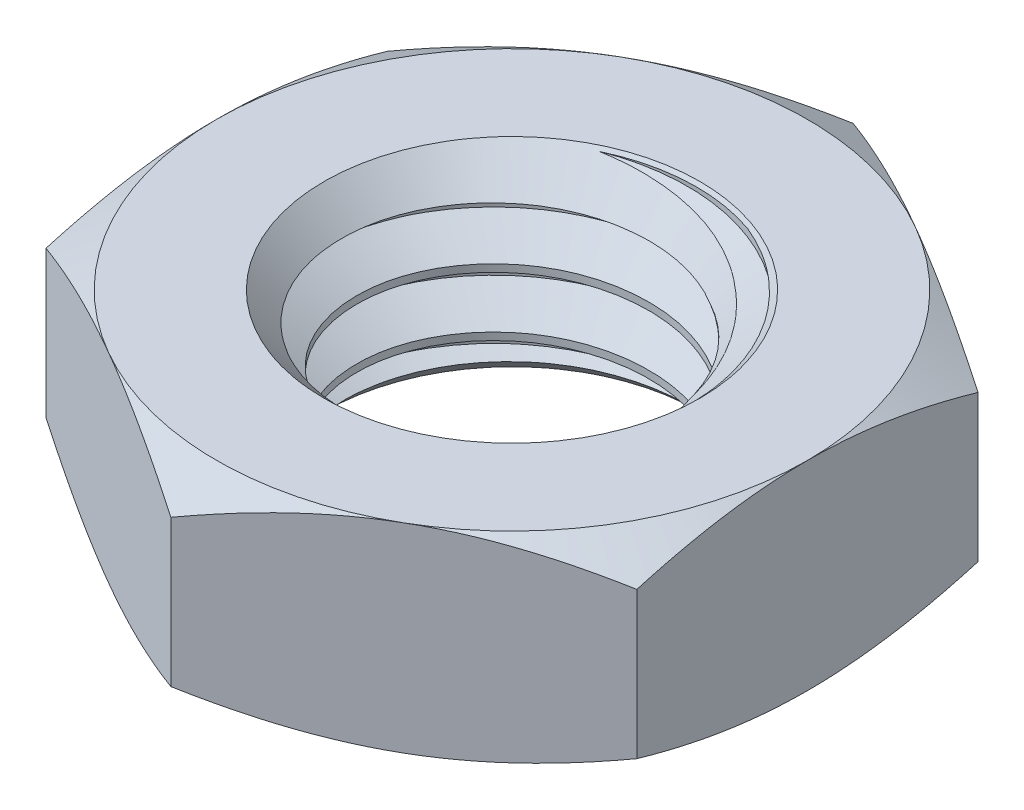
SolidWorks part; units mm, degrees
ref_plane "Front Plane" through (0, 0, 0) normal (0, 0, 1) x (1, 0, 0)
ref_plane "Top Plane" through (0, 0, 0) normal (0, 1, 0) x (1, 0, 0)
ref_plane "Right Plane" through (0, 0, 0) normal (1, 0, 0) x (0, 0, -1)
sketch "Sketch8" plane through (0, 0, 0) normal (0, 1, 0) x (1, 0, 0)
  line L0 (-4, 0) -> (4, 0) construction
  line L1 (0, 2.5) -> (0, -2.5) construction
  line L2 (0, 2.5) -> (-0.8, 2.5) construction
  line L3 (4, -1.35) -> (4, 1.35) construction
  point P4 (0, 0)
  point P8 (0, 0)
  point P11 (4, 0)
  dimension "Hex Size" = 8
  dimension "Thread Size" = 5
  dimension "Pitch" = 0.8
  dimension "Hex Height" = 2.7
sketch "Sketch1" plane through (0, 0, 0) normal (0, 1, 0) x (1, 0, 0)
  line L1 (-4, 2.3094) -> (-4, -2.3094)
  line L2 (-4, -2.3094) -> (0, -4.6188)
  line L3 (0, -4.6188) -> (4, -2.3094)
  line L4 (4, -2.3094) -> (4, 2.3094)
  line L5 (4, 2.3094) -> (0, 4.6188)
  line L6 (0, 4.6188) -> (-4, 2.3094)
  circle A0 centre (0, 0) radius 4 construction
  circle A1 centre (0, 0) radius 2.5
  dimension "Thread Size" = 5
  dimension "Hex" = 8
extrude "Boss-Extrude1" add sketch "Sketch1" along normal mid plane 2.7
sketch "Sketch5" plane through (0, 1.35, 0) normal (0, 1, 0) x (1, 0, 0)
  line L0 (-4, 2.3094) -> (-4, -2.3094) construction
  circle A1 centre (0, 0) radius 4
  circle A2 centre (0, 0) radius 2.5 construction
extrude "Cut-Extrude2" cut sketch "Sketch5" against normal through all draft 60 flip side to cut
mirror "Mirror1" about plane through (0, 0, 0) normal (0, 1, 0) of "Cut-Extrude2"
sketch "Sketch2" plane through (0, 1.35, 0) normal (0, 1, 0) x (1, 0, 0)
  circle A0 centre (0, 0) radius 2.5 construction
  circle A1 centre (0, 0) radius 2.5
sketch "Sketch7" plane through (0, 0, 0) normal (0, 1, 0) x (1, 0, 0)
  line L0 (0, 0) -> (1.25, -2.1651)
  line L1 (0, 0) -> (-2.5, 0) construction
  circle A0 centre (0, 0) radius 2.5 construction
  dimension "D1" = 120
curve "Helix/Spiral1" pitch 0.8 height 3.5 radius 2.5 centre (0, 1.35, 0) axis (0, -1, 0) start towards (0, 0, 1) parameters "Pitch"=0.8
sketch "Sketch3" plane through (0, 0, 0) normal (1, 0, 0) x (0, 0, -1)
  line L0 (2.5866, 2.1) -> (2.5866, 1.3) construction
  line L1 (2.5866, 1.3) -> (1.8938, 1.7) construction
  line L2 (1.8938, 1.7) -> (2.5866, 2.1) construction
  line L3 (2.5866, 1.7) -> (2.5, 1.7) construction
  line L4 (2.5, 1.7) -> (1.9804, 1.7) construction
  line L5 (1.9804, 1.7) -> (1.8938, 1.7) construction
  line L7 (1.9804, 1.65) -> (1.9804, 1.75)
  line L8 (2.5, 1.35) -> (2.5, 2.05) construction
  line L9 (2.5433, 1.325) -> (2.5433, 2.075)
  line L10 (2.5433, 2.075) -> (1.9804, 1.75)
  line L11 (2.5433, 1.325) -> (1.9804, 1.65)
  point P9 (1.9804, 1.7)
  point P12 (2.5, 1.7)
  point P16 (2.5433, 1.7)
  dimension "D1" = 0.8
  dimension "D2" = 0.1
sweep "Sweep1" add profiles "Sketch3" path "Helix/Spiral1"
sketch "Sketch4" plane through (0, 1.35, 0) normal (0, 1, 0) x (1, 0, 0)
  circle A2 centre (0, 0) radius 2.5433
extrude "Cut-Extrude1" cut sketch "Sketch4" along normal through all and the other way through all draft 45
mirror "Mirror2" about plane through (0, 0, 0) normal (0, 1, 0) of "Cut-Extrude1"
equation "\"D3@Helix/Spiral1\"=\"Hex Height@Sketch8\"+\"Pitch@Sketch8\""
equation "\"Height@Boss-Extrude1\"=\"Hex Height@Sketch8\""
equation "\"Thread Size@Sketch1\"=\"Thread Size@Sketch8\""
equation "\"Hex@Sketch1\"=\"Hex Size@Sketch8\""
equation "\"Pitch@Helix/Spiral1\"=\"Pitch@Sketch8\""
equation "\"D1@Sketch3\"=\"Pitch@Sketch8\""
equation "\"D2@Sketch3\"=\"D1@Sketch3\"/8"
